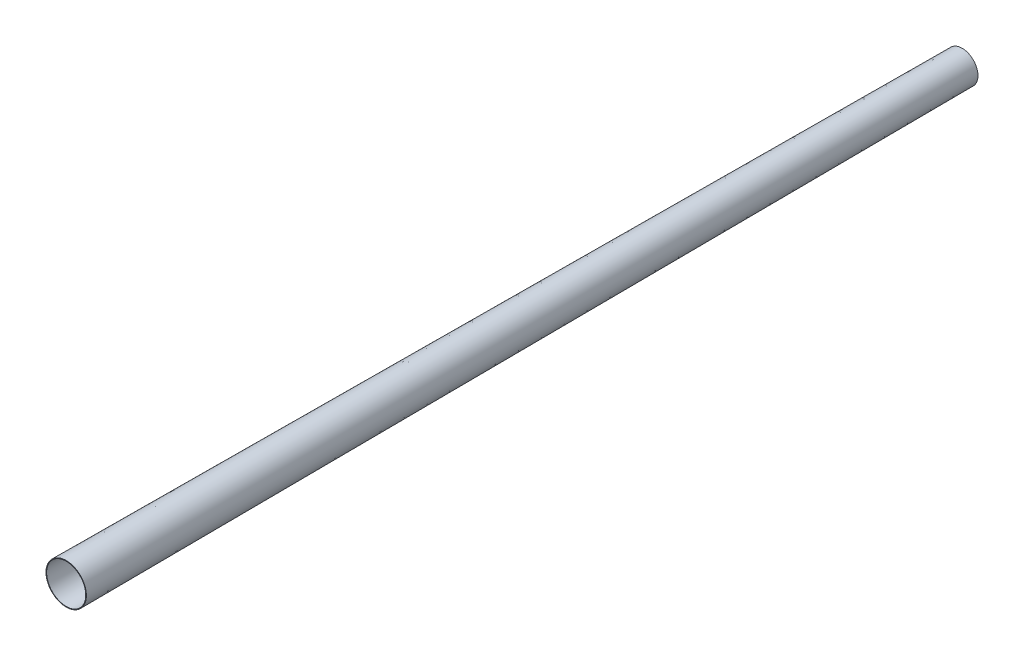
SolidWorks part; units mm, degrees
ref_plane "Front Plane" through (0, 0, 0) normal (0, 0, 1) x (1, 0, 0)
ref_plane "Top Plane" through (0, 0, 0) normal (0, 1, 0) x (1, 0, 0)
ref_plane "Right Plane" through (0, 0, 0) normal (1, 0, 0) x (0, 0, -1)
sketch "Sketch1" plane through (0, 0, 0) normal (0, 0, 1) x (1, 0, 0)
  circle A0 centre (0, 0) radius 11.9044
  circle A1 centre (0, 0) radius 12.4044
  dimension "D2" = 24.8088
  dimension "D1" = 0.5
ref_plane "Plane1" through (0, 0, 700.9946) normal (0, 0, 1) x (1, 0, 0)
sketch "Sketch2" plane through (0, 0, 700.9946) normal (0, 0, 1) x (1, 0, 0)
  circle A0 centre (0, 0) radius 15.8156
  circle A1 centre (0, 0) radius 15.3156
  dimension "D2" = 31.6312
  dimension "D1" = 0.5
loft "Loft1" add section "Sketch1" section "Sketch2" start constraint default connector at (-11.2205, -5.2886, 0) connector at (-14.3273, -6.698, 700.9946)
shell "Shell1" thickness 0.5 removed face at (12.4044, 0, 0) removed face at (15.8156, 0, 700.9946)
